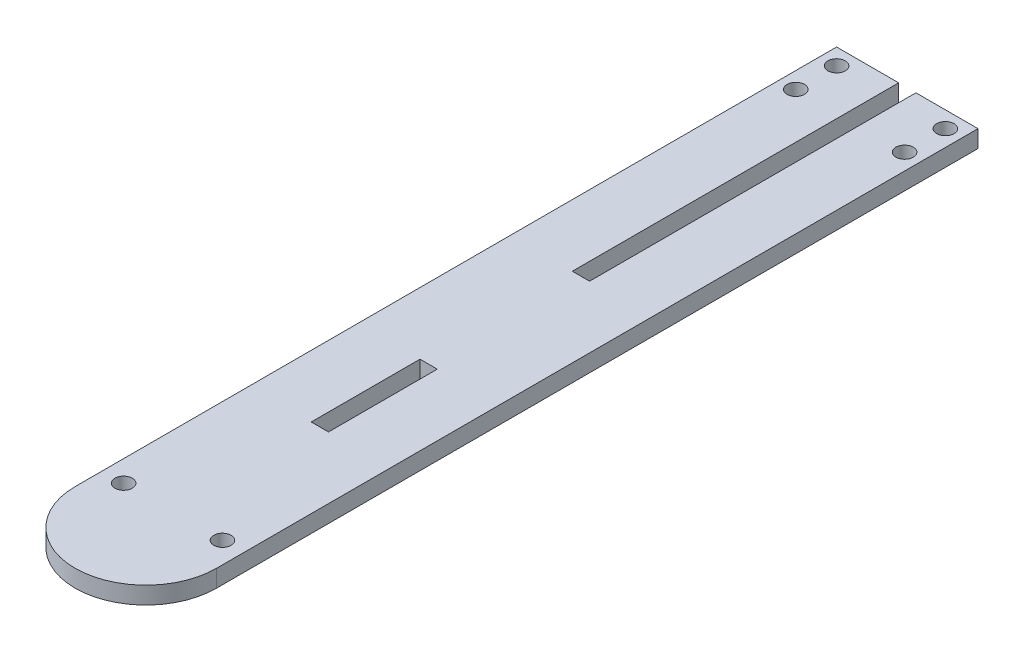
SolidWorks part; units mm, degrees
ref_plane "Front Plane" through (0, 0, 0) normal (0, 0, 1) x (1, 0, 0)
ref_plane "Top Plane" through (0, 0, 0) normal (0, 1, 0) x (1, 0, 0)
ref_plane "Right Plane" through (0, 0, 0) normal (1, 0, 0) x (0, 0, -1)
sketch "Sketch1" plane through (0, 0, 0) normal (0, 1, 0) x (1, 0, 0)
  line L1 (-14.5875, 0) -> (-14.5875, -140)
  line L2 (11.4125, 0) -> (11.4125, -140)
  line L3 (-14.5875, 0) -> (-3.175, 0)
  line L5 (-3.175, 0) -> (-3.175, -60)
  line L6 (-3.175, -60) -> (0, -60)
  line L7 (0, 0) -> (0, -60)
  line L8 (11.4125, 0) -> (0, 0)
  line L9 (0, -48) -> (-3.175, -48) construction
  line L10 (-3.175, -88) -> (0, -88)
  line L11 (-3.175, -88) -> (-3.175, -108)
  line L12 (-3.175, -108) -> (0, -108)
  line L13 (0, -88) -> (0, -108)
  arc A0 (-14.5875, -140) -> (11.4125, -140) centre (-1.5875, -140) ccw
  point P6 (-8.8812, 0)
  dimension "D1" = 26
  dimension "D2" = 140
  dimension "D3" = 3.175
  dimension "D4" = 60
  dimension "D5" = 20
  dimension "D6" = 40
  dimension "D7" = 12
extrude "Boss-Extrude1" add sketch "Sketch1" along normal blind 3.175
sketch "Sketch4" plane through (0, 0, 0) normal (0, -1, 0) x (1, 0, 0)
  circle A0 centre (8.4125, 3) radius 1.6 construction
  circle A1 centre (8.4125, 10.5) radius 1.6 construction
  circle A2 centre (-11.5875, 10.5) radius 1.6 construction
  circle A3 centre (-11.5875, 3) radius 1.6 construction
  circle A4 centre (8.4125, 3) radius 1.6
  circle A5 centre (8.4125, 10.5) radius 1.6
  circle A6 centre (-11.5875, 10.5) radius 1.6
  circle A7 centre (-11.5875, 3) radius 1.6
extrude "Cut-Extrude2" cut sketch "Sketch4" against normal through all both and the other way through all
sketch "Sketch5" plane through (0, 3.175, 0) normal (0, 1, 0) x (1, 0, 0)
  circle A0 centre (-10.675, -135) radius 1.6 construction
  circle A1 centre (7.5, -135) radius 1.6 construction
  circle A2 centre (-10.675, -135) radius 1.6
  circle A3 centre (7.5, -135) radius 1.6
extrude "Cut-Extrude3" cut sketch "Sketch5" against normal through all both and the other way through all
